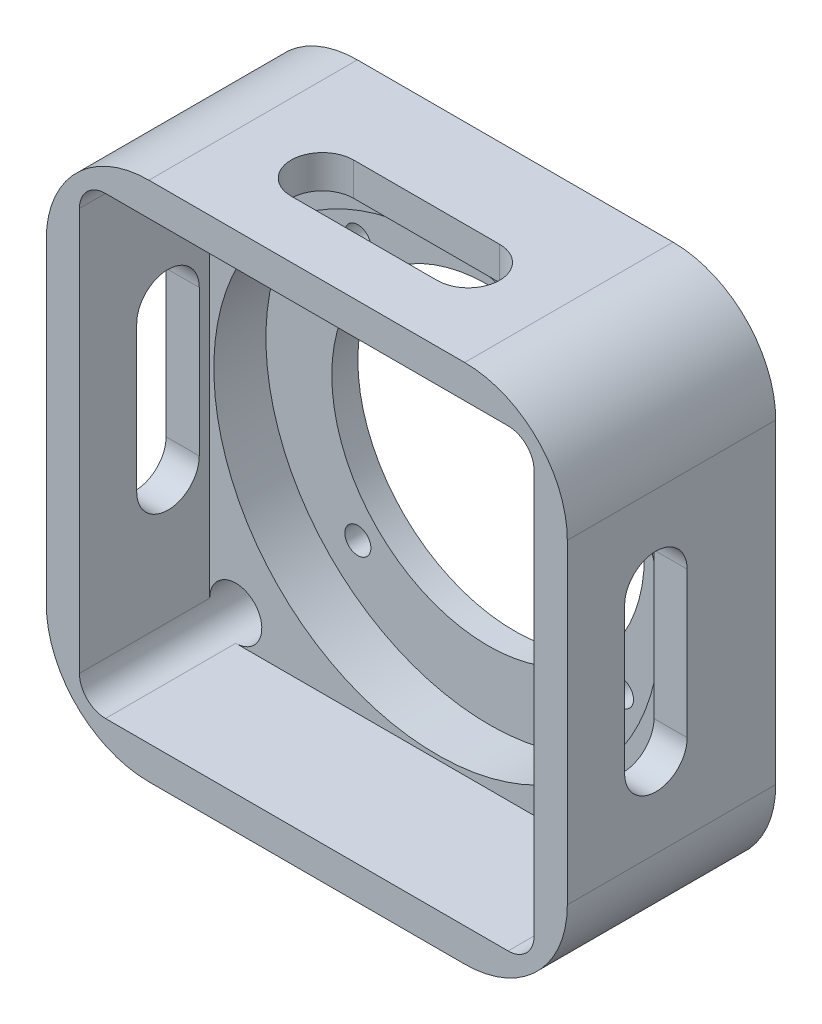
SolidWorks part; units mm, degrees
ref_plane "Front Plane" through (0, 0, 0) normal (0, 0, 1) x (1, 0, 0)
ref_plane "Top Plane" through (0, 0, 0) normal (0, 1, 0) x (1, 0, 0)
ref_plane "Right Plane" through (0, 0, 0) normal (1, 0, 0) x (0, 0, -1)
other "Configuration Table"
sketch "草图1" plane through (0, 0, 0) normal (0, 0, 1) x (1, 0, 0)
  line L0 (0, 0) -> (100.005, 0) construction
  line L1 (0, 93.584) -> (0, -39.2628) construction
  line L2 (44.2281, 44.2281) -> (-44.2281, -44.2281) construction
  line L3 (-30.2935, 50) -> (30.2935, 50)
  line L4 (-50, 30.2935) -> (-50, -30.2935)
  line L5 (-30.2935, -50) -> (30.2935, -50)
  line L6 (50, 30.2935) -> (50, -30.2935)
  line L7 (-44.2281, 44.2281) -> (44.2281, -44.2281) construction
  line L17 (-44.2281, 44.2281) -> (44.2281, -44.2281) construction
  line L18 (-44.2281, -44.2281) -> (44.2281, 44.2281) construction
  circle A0 centre (0, 0) radius 42.8415 construction
  arc A1 (-30.2935, 50) -> (-50, 30.2935) centre (-30.2935, 30.2935) ccw
  arc A2 (30.2935, 50) -> (50, 30.2935) centre (30.2935, 30.2935) cw
  arc A3 (-30.2935, -50) -> (-50, -30.2935) centre (-30.2935, -30.2935) cw
  arc A4 (30.2935, -50) -> (50, -30.2935) centre (30.2935, -30.2935) ccw
  circle A5 centre (-38.635, 38.635) radius 5
  circle A6 centre (38.635, 38.635) radius 5
  circle A7 centre (38.635, -38.635) radius 5
  circle A8 centre (-38.635, -38.635) radius 5
  circle A9 centre (0, 0) radius 42.8415
  dimension "D1" = 100
extrude "凸台-拉伸2" add sketch "草图1" along normal blind 40
extrude "凸台-拉伸3" add sketch "草图1<5>" along normal blind 5 contours A9 region at (0, 0, 0)
sketch "草图1<5>" plane through (0, 0, 0) normal (0, 0, 1) x (1, 0, 0) same geometry as "草图1"
ref_plane "基准面1" through (0, 0, 40) normal (0, 0, -1) x (-1, 0, 0)
sketch "草图4" plane through (0, 0, 40) normal (0, 0, -1) x (-1, 0, 0)
  line L0 (-38.635, 43.635) -> (38.635, 43.635)
  line L1 (-43.635, 38.635) -> (-43.635, -38.635)
  line L2 (-38.635, -43.635) -> (38.635, -43.635)
  line L3 (43.635, 38.635) -> (43.635, -38.635)
  arc A0 (-43.635, 38.635) -> (-38.635, 43.635) centre (-38.635, 38.635) cw
  arc A1 (38.635, 43.635) -> (43.635, 38.635) centre (38.635, 38.635) cw
  arc A2 (38.635, -43.635) -> (43.635, -38.635) centre (38.635, -38.635) ccw
  arc A3 (-43.635, -38.635) -> (-38.635, -43.635) centre (-38.635, -38.635) ccw
extrude "切除-拉伸2" cut sketch "草图4" along normal blind 25
ref_plane "基准面2" through (0, 0, 0) normal (0, 0, -1) x (-1, 0, 0)
sketch "草图5" plane through (0, 0, 0) normal (0, 0, -1) x (-1, 0, 0)
  line L0 (0, 0) -> (0, -36.5435) construction
  circle A11 centre (0.2011, 0.16) radius 30
  circle A12 centre (-24.7989, 25.16) radius 2.5
  circle A13 centre (25.2011, 25.16) radius 2.5
  circle A15 centre (25.2011, -24.84) radius 2.5
  circle A16 centre (-25.2011, -24.84) radius 2.5
extrude "切除-拉伸3" cut sketch "草图5" against normal through all
ref_plane "基准面3" through (0, 0, 15) normal (0, 0, 1) x (1, 0, 0)
ref_plane "基准面4" through (-50, 0, 0) normal (-1, 0, 0) x (0, 0, 1)
sketch "草图7" plane through (-50, 0, 0) normal (-1, 0, 0) x (0, 0, 1)
  line L0 (15, 32.5213) -> (15, -3.6356) construction
  line L1 (23, 14) -> (23, -14) construction
  line L3 (23, 20) -> (23, -20)
  line L4 (0, 0) -> (73.7255, 0) construction
  line L7 (29, 14) -> (29, -14)
  line L8 (17, 14) -> (17, -14)
  arc A0 (29, 14) -> (17, 14) centre (23, 14) ccw
  arc A1 (17, -14) -> (29, -14) centre (23, -14) ccw
  point P14 (23, 0)
  dimension "D1" = 40
extrude "切除-拉伸4" cut sketch "草图7" against normal blind 10 contours A1 L7 A0 L8
ref_plane "基准面5" through (0, 0, 0) normal (1, 0, 0) x (0, 0, -1)
mirror "镜向1" about plane through (0, 0, 0) normal (1, 0, 0) of "切除-拉伸4"
ref_plane "基准面6" through (0, 0, 0) normal (0, -1, 0) x (-1, 0, 0)
ref_plane "基准面8" through (0, -50, 0) normal (0, -1, 0) x (-1, 0, 0)
sketch "草图11" plane through (0, 0, 40) normal (0, 0, -1) x (-1, 0, 0)
  line L0 (0, 0) -> (30.2051, 30.2051)
ref_plane "基准面9" through (0, 0, 0) normal (0.7071, 0.7071, 0) x (0.7071, -0.7071, 0)
mirror "镜向2" about plane through (0, 0, 0) normal (0.7071, 0.7071, 0) of "切除-拉伸4"
ref_plane "基准面10" through (0, 50, 0) normal (0, 1, 0) x (1, 0, 0)
sketch "草图14" plane through (0, 50, 0) normal (0, 1, 0) x (1, 0, 0)
  line L0 (-3.0552, -29) -> (23.9207, -29) construction
  line L1 (-20, -23) -> (20, -23)
  arc A0 (-14, -17) -> (-14, -29) centre (-14, -23) ccw construction
  arc A1 (14, -29) -> (14, -17) centre (14, -23) ccw construction
